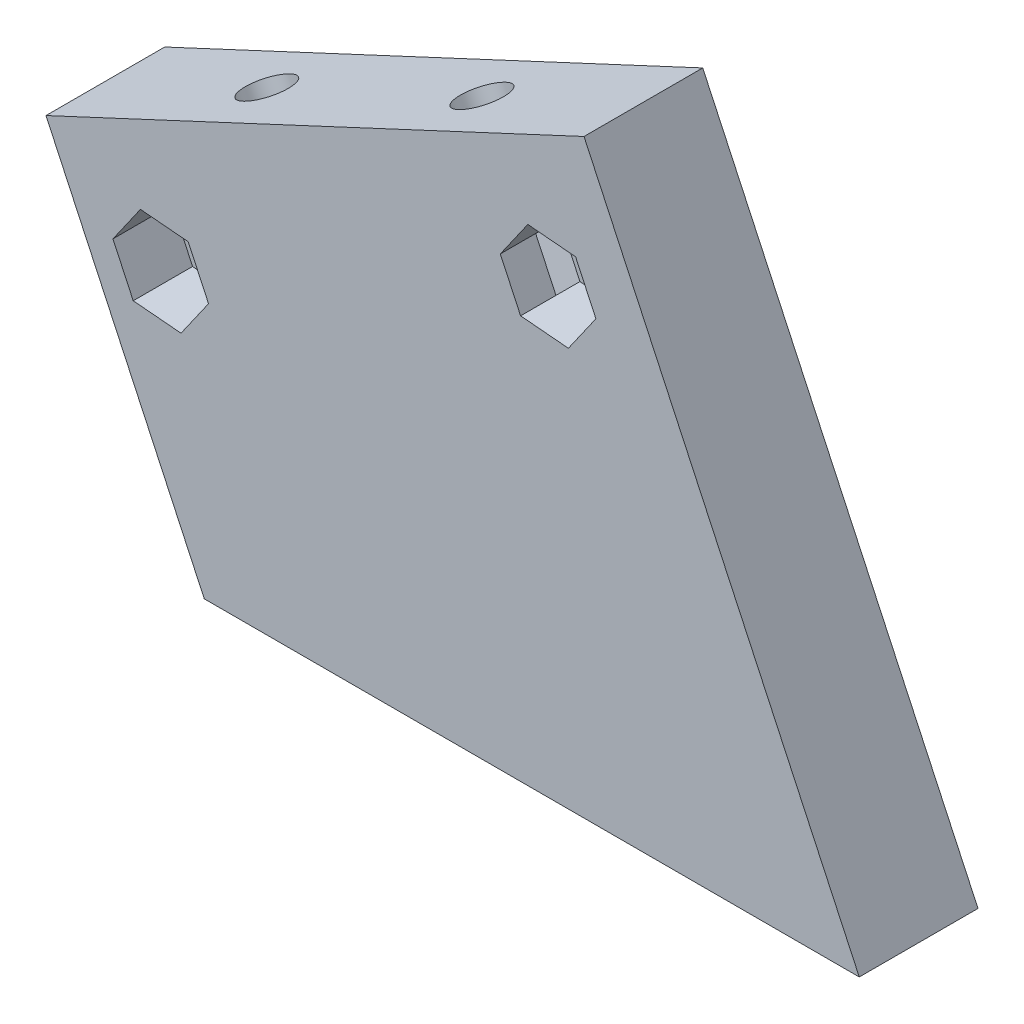
SolidWorks part; units mm, degrees
material "ABS"
ref_plane "Front Plane" through (0, 0, 0) normal (0, 0, 1) x (1, 0, 0)
ref_plane "Top Plane" through (0, 0, 0) normal (0, 1, 0) x (1, 0, 0)
ref_plane "Right Plane" through (0, 0, 0) normal (1, 0, 0) x (0, 0, -1)
sketch "Sketch1" plane through (0, 0, 0) normal (0, 0, 1) x (1, 0, 0)
  line L0 (110.3324, 0.0035) -> (87.1479, 49.7228)
  line L2 (87.1479, 49.7228) -> (41.8325, 28.5919)
  line L3 (41.8325, 28.5919) -> (55.1635, 0.0035)
  line L4 (55.1635, 0.0035) -> (110.3324, 0.0035)
  line L6 (189.2372, 97.3278) -> (-129.7831, -51.4338) construction
  dimension "D1" = 50
extrude "Boss-Extrude1" add sketch "Sketch1" against normal blind 10
sketch "Sketch2" plane through (-3.4798, 7.4624, 0) normal (-0.4226, 0.9063, 0) x (0.9063, 0.4226, 0)
  line L0 (49.9966, 5) -> (99.9966, 5) construction
  line L1 (49.9966, 10) -> (49.9966, 0) construction
  line L2 (99.9966, 10) -> (99.9966, 0) construction
  line L3 (74.9966, 10) -> (74.9966, 0) construction
  line L4 (84.9966, 0.9585) -> (88.4966, 2.9793)
  line L5 (88.4966, 2.9793) -> (88.4966, 7.0207)
  line L6 (88.4966, 7.0207) -> (84.9966, 9.0415)
  line L7 (84.9966, 9.0415) -> (81.4966, 7.0207)
  line L8 (81.4966, 7.0207) -> (81.4966, 2.9793)
  line L9 (81.4966, 2.9793) -> (84.9966, 0.9585)
  line L10 (99.9966, 10) -> (49.9966, 10) construction
  line L11 (99.9966, 0) -> (49.9966, 0) construction
  line L12 (68.4966, 2.9793) -> (64.9966, 0.9585)
  line L13 (64.9966, 0.9585) -> (61.4966, 2.9793)
  line L14 (68.4966, 7.0207) -> (68.4966, 2.9793)
  line L15 (64.9966, 9.0415) -> (68.4966, 7.0207)
  line L16 (61.4966, 7.0207) -> (64.9966, 9.0415)
  line L17 (61.4966, 2.9793) -> (61.4966, 7.0207)
  circle A0 centre (84.9966, 5) radius 3.5 construction
  circle A1 centre (84.9966, 5) radius 2
  circle A2 centre (64.9966, 5) radius 3.5 construction
  circle A3 centre (64.9966, 5) radius 2
  dimension "D3" = 4
  dimension "D1" = 15
  dimension "D2" = 7
extrude "Cut-Extrude1" cut sketch "Sketch2" against normal through all contours A3 | A1 region at (73.5533, 43.3835, -5) region at (55.4272, 34.9312, -5)
extrude "Cut-Extrude2" cut sketch "Sketch2<3>" against normal through all from offset 4 offset against normal yes
sketch "Sketch2<3>" plane through (-3.4798, 7.4624, 0) normal (-0.4226, 0.9063, 0) x (0.9063, 0.4226, 0) same geometry as "Sketch2"
sketch "Sketch3" plane through (0, 0.0035, 0) normal (0, -1, 0) x (1, 0, 0)
  line L0 (110.3324, -5) -> (55.1635, -5) construction
  line L1 (110.3324, -10) -> (110.3324, 0) construction
  line L2 (55.1635, -10) -> (55.1635, 0) construction
  circle A0 centre (82.748, -5) radius 2
  circle A1 centre (102.8324, -5) radius 2
  dimension "D1" = 4
  dimension "D2" = 4
  dimension "D3" = 7.5
extrude "Cut-Extrude3" cut sketch "Sketch3" against normal blind 10
sketch "Sketch4" plane through (0, 0, 0) normal (0, 0, 1) x (1, 0, 0)
  line L0 (110.3324, 0.0035) -> (87.1479, 49.7228) construction
  line L1 (88.1497, 36.9265) -> (86.4417, 40.5893)
  line L2 (86.4417, 40.5893) -> (82.4157, 40.9416)
  line L3 (82.4157, 40.9416) -> (80.0976, 37.631)
  line L4 (80.0976, 37.631) -> (81.8056, 33.9682)
  line L5 (81.8056, 33.9682) -> (85.8317, 33.616)
  line L6 (85.8317, 33.616) -> (88.1497, 36.9265)
  line L7 (87.1479, 49.7228) -> (41.8325, 28.5919) construction
  line L8 (55.5227, 21.7123) -> (53.8147, 25.3751)
  line L9 (53.8147, 25.3751) -> (49.7886, 25.7273)
  line L10 (49.7886, 25.7273) -> (47.4705, 22.4167)
  line L11 (47.4705, 22.4167) -> (49.1785, 18.7539)
  line L12 (49.1785, 18.7539) -> (53.2046, 18.4017)
  line L13 (53.2046, 18.4017) -> (55.5227, 21.7123)
  line L14 (87.1479, 49.7228) -> (41.8325, 28.5919) construction
  line L15 (41.8325, 28.5919) -> (55.1635, 0.0035) construction
  circle A0 centre (84.1237, 37.2788) radius 2
  circle A1 centre (84.1237, 37.2788) radius 3.5 construction
  circle A2 centre (51.4966, 22.0645) radius 2
  circle A3 centre (51.4966, 22.0645) radius 3.5 construction
  dimension "D4" = 4
  dimension "D7" = 4
  dimension "D1" = 8
  dimension "D2" = 10
  dimension "D3" = 7
  dimension "D5" = 0
  dimension "D6" = 7
  dimension "D8" = 10
  dimension "D9" = 6
extrude "Cut-Extrude4" cut sketch "Sketch4" against normal blind 10 contours A0 | A2 region at (84.1237, 37.2788, 0) region at (51.4966, 22.0645, 0)
extrude "Cut-Extrude5" cut sketch "Sketch4<3>" against normal blind 5 from surface starting at face at (86.1237, 37.2788, 0)
sketch "Sketch4<3>" plane through (0, 0, 0) normal (0, 0, 1) x (1, 0, 0) same geometry as "Sketch4"
